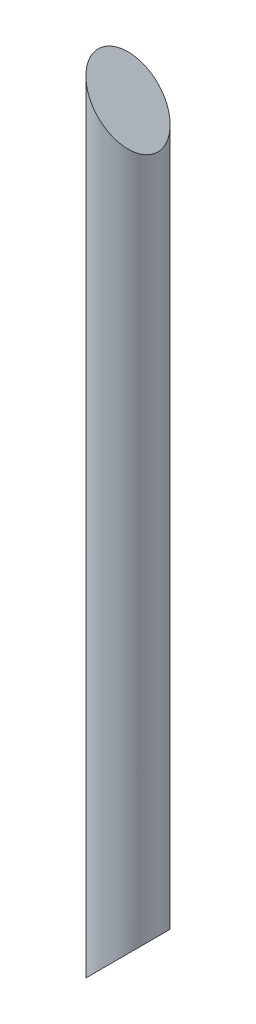
SolidWorks part; units mm, degrees
ref_plane "Front Plane" through (0, 0, 0) normal (0, 0, 1) x (1, 0, 0)
ref_plane "Top Plane" through (0, 0, 0) normal (0, 1, 0) x (1, 0, 0)
ref_plane "Right Plane" through (0, 0, 0) normal (1, 0, 0) x (0, 0, -1)
sketch "Sketch1" plane through (0, 0, 0) normal (0, 1, 0) x (1, 0, 0)
  circle A0 centre (0, 0) radius 31.75
  dimension "D1" = 63.5
extrude "Boss-Extrude1" add sketch "Sketch1" along normal blind 723.9
sketch "Sketch2" plane through (0, 0, 0) normal (0, 0, 1) x (1, 0, 0)
  line L0 (-31.75, 723.9) -> (31.75, 723.9)
  line L1 (31.75, 723.9) -> (31.75, 787.4)
  line L3 (31.75, 787.4) -> (-31.75, 787.4)
  line L4 (-31.75, 787.4) -> (-31.75, 723.9)
  line L5 (31.75, 0) -> (-31.75, 0)
  line L6 (-31.75, 0) -> (-31.75, -63.5)
  line L7 (-31.75, -63.5) -> (31.75, 0)
  line L8 (-31.75, -63.5) -> (31.75, -63.5)
  line L9 (31.75, -63.5) -> (31.75, 0)
  line L11 (31.75, 723.9) -> (-31.75, 787.4)
  dimension "D1" = 45
  dimension "D2" = 45
sketch "Sketch3" plane through (0, 0, 0) normal (0, -1, 0) x (1, 0, 0)
  circle A0 centre (0, 0) radius 31.75
sketch "Sketch4" plane through (0, 723.9, 0) normal (0, 1, 0) x (1, 0, 0)
  circle A0 centre (0, 0) radius 31.75
extrude "Boss-Extrude2" add sketch "Sketch4" along normal blind 63.5
sketch "Sketch5" plane through (0, 0, 0) normal (0, -1, 0) x (1, 0, 0)
  circle A0 centre (0, 0) radius 31.75
extrude "Boss-Extrude3" add sketch "Sketch5" along normal blind 63.5
extrude "Cut-Extrude2" cut sketch "Sketch2" against normal blind 63.5 and the other way blind 63.5 contours L8 L9 L7 | L11 L1 L3 region at (10.5833, 766.2333, 0) region at (10.5833, -42.3333, 0)
